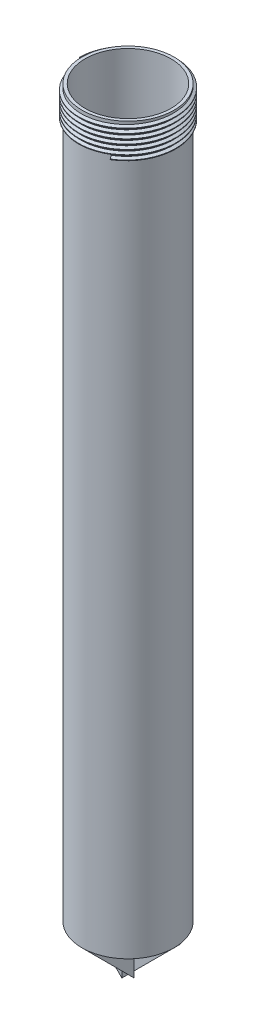
SolidWorks part; units mm, degrees
ref_plane "Front Plane" through (0, 0, 0) normal (0, 0, 1) x (1, 0, 0)
ref_plane "Top Plane" through (0, 0, 0) normal (0, 1, 0) x (1, 0, 0)
ref_plane "Right Plane" through (0, 0, 0) normal (1, 0, 0) x (0, 0, -1)
sketch "Sketch1" plane through (0, 0, 0) normal (0, 1, 0) x (1, 0, 0)
  circle A0 centre (0, 0) radius 15
  dimension "D1" = 30
extrude "Extrude-Thin1" add sketch "Sketch1" along normal blind 236.22 thin thin type one direction reverse wall 1
thread "Thread1" pitch 1.5 method extrude profile "Thread Profile1" start angle 0, offset 0, length 10, pitch 1.5, diameter 30
ref_plane "Plane1" through (-15, 236.22, 0) normal (0, 0, 1) x (-1, 0, 0)
sketch "Thread Profile1" plane through (-15, 236.22, 0) normal (0, 0, 1) x (-1, 0, 0)
  line L0 (0, 0) -> (0, 1.5) construction
  line L1 (0, 0) -> (0.8119, 0.4687)
  line L2 (0.8119, 0.4687) -> (0.8119, 0.6562)
  line L3 (0.8119, 0.6562) -> (0, 1.125)
  line L4 (0.8119, 0.5625) -> (0, 0.5625) construction
  line L11 (0, 0) -> (0, 1.125)
  point P2 (0, 0)
  dimension "Pitch" = 1.5
  dimension "Profile_Angle" = 60
  dimension "Profile_Land" = 0.1875
  dimension "Profile_Height" = 0.8119
sketch "Sketch2" plane through (0, 0, 0) normal (0, 0, 1) x (1, 0, 0)
  line L0 (-15, 0) -> (0, -15)
  line L1 (0, -15) -> (0, -7.9289)
  line L2 (0, -7.9289) -> (-7.9289, 0)
  line L3 (-15, 0) -> (15, 0) construction
  line L4 (-15, 0) -> (-7.9289, 0)
  dimension "D1" = 5
  dimension "D2" = 45
extrude "Boss-Extrude1" add sketch "Sketch2" along normal blind 2
pattern_circular "CirPattern1" count 4 over 360 about axis through (0, 0, 0) along (0, 1, 0) of "Boss-Extrude1"
equation "\"0.035n\"=0.03"
